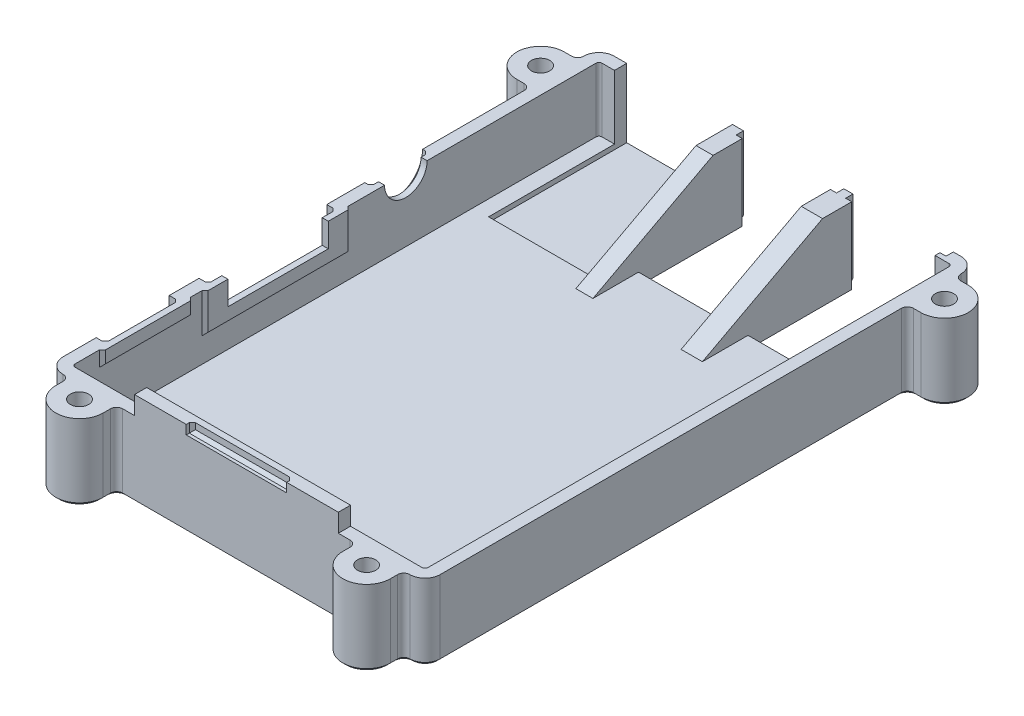
SolidWorks part; units mm, degrees
ref_plane "Front Plane" through (0, 0, 0) normal (0, 0, 1) x (1, 0, 0)
ref_plane "Top Plane" through (0, 0, 0) normal (0, 1, 0) x (1, 0, 0)
ref_plane "Right Plane" through (0, 0, 0) normal (1, 0, 0) x (0, 0, -1)
sketch "Sketch2" plane through (0, 0, 0) normal (0, 1, 0) x (1, 0, 0)
  line L1 (2.5, 0) -> (59.5, 0)
  line L2 (0, 2.5) -> (0, 88.1)
  line L3 (2.5, 90.6) -> (59.5, 90.6)
  line L4 (62, 2.5) -> (62, 88.1)
  arc A0 (0, 2.5) -> (2.5, 0) centre (2.5, 2.5) ccw
  arc A1 (59.5, 0) -> (62, 2.5) centre (59.5, 2.5) ccw
  arc A2 (62, 88.1) -> (59.5, 90.6) centre (59.5, 88.1) ccw
  arc A3 (2.5, 90.6) -> (0, 88.1) centre (2.5, 88.1) ccw
  point P7 (0, 0)
  point P10 (62, 0)
  point P13 (62, 90.6)
  point P16 (0, 90.6)
  dimension "D3" = 2.5
  dimension "D1" = 62
  dimension "D2" = 90.6
extrude "Base" add sketch "Sketch2" along normal blind 12.5
shell "Shell" thickness 2 removed face at (31, 12.5, -45.3)
sketch "Sketch14" plane through (0, 0, 0) normal (0, -1, 0) x (1, 0, 0)
  line L0 (31, 0) -> (31, -90.6) construction
  line L2 (59.5, -90.6) -> (2.5, -90.6) construction
  line L3 (-2.2, -79.3) -> (0, -79.3)
  line L4 (0, -88.1) -> (0, -2.5) construction
  line L5 (0, -79.3) -> (0, -87.1)
  line L6 (0, -87.1) -> (-2.2, -87.1)
  line L7 (3.5, 2.2) -> (3.5, 0)
  line L8 (2.5, 0) -> (59.5, 0) construction
  line L9 (3.5, 0) -> (11.3, 0)
  line L10 (11.3, 0) -> (11.3, 2.2)
  line L11 (64.2, -79.3) -> (62, -79.3)
  line L12 (62, -87.1) -> (64.2, -87.1)
  line L13 (62, -79.3) -> (62, -87.1)
  line L14 (50.7, 0) -> (50.7, 2.2)
  line L15 (58.5, 0) -> (50.7, 0)
  line L16 (58.5, 2.2) -> (58.5, 0)
  line L17 (2.5, 0) -> (59.5, 0) construction
  arc A0 (-2.2, -79.3) -> (-2.2, -87.1) centre (-2.2, -83.2) ccw
  arc A1 (3.5, 2.2) -> (11.3, 2.2) centre (7.4, 2.2) cw
  arc A2 (64.2, -79.3) -> (64.2, -87.1) centre (64.2, -83.2) cw
  arc A3 (58.5, 2.2) -> (50.7, 2.2) centre (54.6, 2.2) ccw
  dimension "D1" = 2.2
  dimension "D2" = 7.8
  dimension "D3" = 3.5
  dimension "D4" = 3.5
extrude "Clamps" add sketch "Sketch14" against normal up to surface (12.5 mm away) up to face at (31, 12.5, -45.3)
fillet "Clamp Fillets" radius 1 8 edges at (50.7, 6.25, 0) (58.5, 6.25, 0) (11.3, 6.25, 0) (3.5, 6.25, 0) (0, 6.25, -87.1) (0, 6.25, -79.3) (62, 6.25, -79.3) (62, 6.25, -87.1)
sketch "Sketch20" plane through (0, 0, 0) normal (0, -1, 0) x (1, 0, 0)
  circle A0 centre (7.4, 2.2) radius 1.5
  circle A1 centre (54.6, 2.2) radius 1.5
  circle A2 centre (64.2, -83.2) radius 1.5
  circle A3 centre (-2.2, -83.2) radius 1.5
  arc A4 (11.3, 2.2) -> (3.5, 2.2) centre (7.4, 2.2) ccw construction
  arc A5 (58.5, 2.2) -> (50.7, 2.2) centre (54.6, 2.2) ccw construction
  arc A6 (-2.2, -79.3) -> (-2.2, -87.1) centre (-2.2, -83.2) ccw construction
  arc A7 (64.2, -87.1) -> (64.2, -79.3) centre (64.2, -83.2) ccw construction
  dimension "D1" = 3
extrude "Clamp Holes" cut sketch "Sketch20" against normal through all
sketch "Sketch21" plane through (0, 0, 0) normal (0, -1, 0) x (1, 0, 0)
  circle A0 centre (7.4, 2.2) radius 2.5
  circle A1 centre (54.6, 2.2) radius 2.5
  circle A2 centre (64.2, -83.2) radius 2.5
  circle A3 centre (-2.2, -83.2) radius 2.5
  circle A4 centre (-2.2, -83.2) radius 1.5 construction
  circle A5 centre (7.4, 2.2) radius 1.5 construction
  circle A6 centre (54.6, 2.2) radius 1.5 construction
  circle A7 centre (64.2, -83.2) radius 1.5 construction
  dimension "D1" = 5
extrude "Clamp Countersinks" cut sketch "Sketch21" against normal blind 3
chamfer "Clamp Countersink Chamfers" distance 0.3 angle 45 4 edges at (-2.2, 0, -85.7) (64.2, 0, -85.7) (54.6, 0, -0.3) (7.4, 0, -0.3)
sketch "Sketch22" plane through (0, 12.5, 0) normal (0, 1, 0) x (1, 0, 0)
  line L0 (31, 2) -> (31, 0) construction
  line L1 (2.5, 2) -> (59.5, 2) construction
  line L2 (12.3, 0) -> (49.7, 0) construction
  line L4 (14.25, 2) -> (47.75, 2)
  line L5 (14.25, 2) -> (14.25, 0)
  line L6 (14.25, 0) -> (47.75, 0)
  line L7 (47.75, 2) -> (47.75, 0)
  dimension "D1" = 16.75
  dimension "D2" = 33.5
extrude "SD Fill" add sketch "Sketch22" along normal blind 3
sketch "Sketch23" plane through (0, 0, 0) normal (0, 0, 1) x (1, 0, 0)
  line L0 (31, 15.5) -> (31, 0) construction
  line L1 (14.25, 15.5) -> (47.75, 15.5) construction
  line L2 (12.3, 0) -> (49.7, 0) construction
  line L4 (22.75, 15.5) -> (39.25, 15.5)
  line L5 (22.75, 15.5) -> (22.75, 14)
  line L6 (22.75, 14) -> (39.25, 14)
  line L7 (39.25, 15.5) -> (39.25, 14)
  dimension "D1" = 8.25
  dimension "D2" = 16.5
  dimension "D3" = 1.5
extrude "SD Approach" cut sketch "Sketch23" against normal blind 1
chamfer "SD Approach Chamfer" distance 0.5 angle 45 3 edges at (39.25, 14.75, -1) (31, 14, -1) (22.75, 14.75, -1)
sketch "Sketch24" plane through (0, 0, -90.6) normal (0, 0, -1) x (-1, 0, 0)
  line L0 (-59.5, 12.5) -> (-2.5, 12.5) construction
  line L1 (-57.25, 12.5) -> (-42.75, 12.5)
  line L2 (-57.25, 12.5) -> (-57.25, 0)
  line L3 (-57.25, 0) -> (-42.75, 0)
  line L4 (-42.75, 12.5) -> (-42.75, 0)
  line L5 (-59.5, 0) -> (-2.5, 0) construction
  line L6 (0, 12.5) -> (0, 0) construction
  line L7 (-39.25, 12.5) -> (-24.75, 12.5)
  line L8 (-39.25, 12.5) -> (-39.25, 0)
  line L9 (-39.25, 0) -> (-24.75, 0)
  line L10 (-24.75, 12.5) -> (-24.75, 0)
  dimension "D1" = 14.5
  dimension "D2" = 24.75
  dimension "D3" = 42.75
extrude "USB Cutout" cut sketch "Sketch24" against normal blind 18.25
sketch "Sketch25" plane through (0, 0, -90.6) normal (0, 0, -1) x (-1, 0, 0)
  line L0 (-42.75, 12.5) -> (-39.25, 12.5) construction
  line L1 (-41.75, 12.5) -> (-58.25, 12.5)
  line L2 (-41.75, 12.5) -> (-41.75, 0)
  line L3 (-41.75, 0) -> (-58.25, 0)
  line L4 (-58.25, 12.5) -> (-58.25, 0)
  line L5 (-59.5, 0) -> (-57.25, 0) construction
  line L6 (-24.75, 12.5) -> (-2.5, 12.5) construction
  line L7 (-23.75, 12.5) -> (-40.25, 12.5)
  line L8 (-23.75, 12.5) -> (-23.75, 0)
  line L9 (-23.75, 0) -> (-40.25, 0)
  line L10 (-40.25, 12.5) -> (-40.25, 0)
  line L11 (-42.75, 0) -> (-39.25, 0) construction
  line L12 (-57.25, 12.5) -> (-57.25, 0) construction
  line L13 (-42.75, 0) -> (-42.75, 12.5) construction
  line L14 (-39.25, 12.5) -> (-39.25, 0) construction
  line L15 (-24.75, 0) -> (-24.75, 12.5) construction
  point P18 (-57.25, 6.25)
  dimension "D1" = 1
  dimension "D2" = 1
  dimension "D3" = 1
  dimension "D4" = 1
extrude "USB Approach" cut sketch "Sketch25" against normal blind 1.2
sketch "Sketch26" plane through (42.75, 0, 0) normal (1, 0, 0) x (0, 0, -1)
  line L0 (88.6, 2) -> (88.6, 12.5)
  line L1 (88.6, 12.5) -> (84.6, 12.5)
  line L2 (88.6, 2) -> (64.8524, 2)
  line L3 (64.8524, 2) -> (84.6, 12.5)
  line L4 (90.6, 0) -> (90.6, 12.5) construction
  dimension "D1" = 6
  dimension "D2" = 28
extrude "USB Inner Support" add sketch "Sketch26" against normal up to surface (3.5 mm away) up to face at (39.25, 4.8333, -83.45)
sketch "Sketch27" plane through (24.75, 0, 0) normal (1, 0, 0) x (0, 0, -1)
  line L0 (88.6, 2) -> (88.6, 12.5)
  line L1 (88.6, 12.5) -> (84.6, 12.5)
  line L2 (88.6, 2) -> (64.8524, 2)
  line L3 (64.8524, 2) -> (84.6, 12.5)
  line L4 (90.6, 0) -> (90.6, 12.5) construction
  dimension "D1" = 6
  dimension "D2" = 28
extrude "USB Outer Support" add sketch "Sketch27" against normal blind 2.8
sketch "Sketch28" plane through (0, 0, -90.6) normal (0, 0, -1) x (-1, 0, 0)
  line L0 (-23.75, 12.5) -> (-2.5, 12.5) construction
  line L1 (-21.95, 12.5) -> (-4.55, 12.5)
  line L2 (-21.95, 12.5) -> (-21.95, 1.2)
  line L3 (-21.95, 1.2) -> (-4.55, 1.2)
  line L4 (-4.55, 12.5) -> (-4.55, 1.2)
  line L5 (0, 12.5) -> (0, 0) construction
  dimension "D1" = 17.4
  dimension "D2" = 4.55
  dimension "D3" = 11.3
extrude "RJ45 Cutout" cut sketch "Sketch28" against normal blind 22.7
sketch "Sketch29" plane through (2, 0, 0) normal (1, 0, 0) x (0, 0, -1)
  line L0 (88.1, 12.5) -> (2.5, 12.5) construction
  line L1 (6.45, 12.5) -> (21.45, 12.5)
  line L2 (6.45, 12.5) -> (6.45, 10)
  line L3 (6.45, 10) -> (21.45, 10)
  line L4 (21.45, 12.5) -> (21.45, 10)
  line L5 (0, 12.5) -> (0, 0) construction
  line L6 (23.35, 12.5) -> (47.35, 12.5)
  line L7 (23.35, 12.5) -> (23.35, 6.07)
  line L8 (23.35, 6.07) -> (47.35, 6.07)
  line L9 (47.35, 12.5) -> (47.35, 6.07)
  dimension "D1" = 24
  dimension "D2" = 15
  dimension "D3" = 6.45
  dimension "D4" = 23.35
  dimension "D5" = 2.5
  dimension "D6" = 6.43
extrude "HDMI Support" add sketch "Sketch29" along normal blind 0.5
chamfer "HDMI Support Chamfer" distance 0.5 angle 45 6 edges at (2.5, 9.285, -47.35) (2.5, 6.07, -35.35) (2.5, 9.285, -23.35) (2.5, 11.25, -21.45) (2.5, 10, -13.95) (2.5, 11.25, -6.45)
sketch "Sketch30" plane through (0, 0, 0) normal (-1, 0, 0) x (0, 0, 1)
  line L0 (-78.3, 12.5) -> (-2.5, 12.5) construction
  line L1 (-24.85, 12.5) -> (-45.85, 12.5)
  line L2 (-24.85, 12.5) -> (-24.85, 6.57)
  line L3 (-24.85, 6.57) -> (-45.85, 6.57)
  line L4 (-45.85, 12.5) -> (-45.85, 6.57)
  line L5 (0, 12.5) -> (0, 0) construction
  line L6 (-19.95, 12.5) -> (-7.95, 12.5)
  line L7 (-19.95, 12.5) -> (-19.95, 10.5)
  line L8 (-19.95, 10.5) -> (-7.95, 10.5)
  line L9 (-7.95, 12.5) -> (-7.95, 10.5)
  dimension "D1" = 12
  dimension "D2" = 21
  dimension "D3" = 7.95
  dimension "D4" = 24.85
  dimension "D5" = 5.93
  dimension "D6" = 2
extrude "HDMI Approach" cut sketch "Sketch30" against normal blind 1.5
sketch "Sketch31" plane through (1.5, 0, 0) normal (-1, 0, 0) x (0, 0, 1)
  line L0 (-24.85, 12.5) -> (-45.85, 12.5) construction
  line L1 (-43.6, 12.5) -> (-27.1, 12.5)
  line L2 (-43.6, 12.5) -> (-43.6, 8.57)
  line L3 (-43.6, 8.57) -> (-27.1, 8.57)
  line L4 (-27.1, 12.5) -> (-27.1, 8.57)
  line L5 (-45.85, 12.5) -> (-45.85, 6.57) construction
  line L6 (-24.85, 6.57) -> (-24.85, 12.5) construction
  line L7 (-45.85, 6.57) -> (-24.85, 6.57) construction
  dimension "D1" = 2.25
  dimension "D2" = 2.25
  dimension "D3" = 2
extrude "HDMI Cutout" cut sketch "Sketch31" against normal blind 1
chamfer "HDMI Approach Chamfer" distance 0.5 angle 45 6 edges at (1.5, 11.5, -7.95) (1.5, 10.5, -13.95) (1.5, 11.5, -19.95) (1.5, 9.535, -24.85) (1.5, 6.57, -35.35) (1.5, 9.535, -45.85)
sketch "Sketch32" plane through (0, 0, 0) normal (-1, 0, 0) x (0, 0, 1)
  line L0 (-78.3, 12.5) -> (-45.85, 12.5) construction
  line L1 (0, 12.5) -> (0, 0) construction
  circle A0 centre (-56.85, 12.5) radius 3.5
  dimension "D1" = 7
  dimension "D2" = 56.85
extrude "Audio Cutout" cut sketch "Sketch32" against normal blind 2
sketch "Sketch33" plane through (0, 0, 0) normal (-1, 0, 0) x (0, 0, 1)
  circle A0 centre (-56.85, 12.5) radius 4.75
  arc A1 (-60.35, 12.5) -> (-53.35, 12.5) centre (-56.85, 12.5) ccw construction
  dimension "D1" = 9.5
extrude "Audio Approach" cut sketch "Sketch33" against normal blind 1
chamfer "Audio Approach Chamfer" distance 0.5 angle 45 1 edges at (1, 7.75, -56.85)
sketch "Sketch34" plane through (0, 0, 0) normal (0, -1, 0) x (1, 0, 0)
  line L0 (62, -2.5) -> (62, -78.3) construction
  line L1 (52.5, -9.4) -> (58.5, -9.4)
  line L2 (52.5, -9.4) -> (52.5, -62.1)
  line L3 (52.5, -62.1) -> (58.5, -62.1)
  line L4 (58.5, -9.4) -> (58.5, -62.1)
  line L5 (12.3, 0) -> (49.7, 0) construction
  point P6 (55.5, -9.4)
  dimension "D1" = 6
  dimension "D2" = 52.7
  dimension "D3" = 3.5
  dimension "D4" = 9.4
extrude "Header Cutout" cut sketch "Sketch34" against normal blind 2
sketch "Sketch35" plane through (0, 0, 0) normal (0, -1, 0) x (1, 0, 0)
  line L0 (55.5, -9.4) -> (55.5, -62.1) construction
  line L1 (58.5, -9.4) -> (52.5, -9.4) construction
  line L2 (52.5, -62.1) -> (58.5, -62.1) construction
  line L3 (52.5, -35.75) -> (58.5, -35.75) construction
  line L4 (52.5, -9.4) -> (52.5, -62.1) construction
  line L5 (58.5, -62.1) -> (58.5, -9.4) construction
  line L6 (56, -9.4) -> (55, -9.4)
  line L7 (55, -9.4) -> (55, -10.4)
  line L8 (55, -10.4) -> (53.5, -10.4)
  line L9 (53.5, -10.4) -> (53.5, -15.3625)
  line L10 (53.5, -15.3625) -> (52.5, -15.3625)
  line L11 (52.5, -15.3625) -> (52.5, -16.3625)
  line L12 (52.5, -16.3625) -> (53.5, -16.3625)
  line L13 (53.5, -16.3625) -> (53.5, -28.2875)
  line L14 (53.5, -28.2875) -> (52.5, -28.2875)
  line L15 (52.5, -28.2875) -> (52.5, -29.2875)
  line L16 (52.5, -29.2875) -> (53.5, -29.2875)
  line L17 (53.5, -29.2875) -> (53.5, -34.25)
  line L18 (53.5, -34.25) -> (55, -34.25)
  line L19 (55, -34.25) -> (55, -35.25)
  line L20 (55, -35.25) -> (52.5, -35.25)
  line L21 (52.5, -35.25) -> (52.5, -36.25)
  line L22 (56, -62.1) -> (55, -62.1)
  line L23 (55, -36.25) -> (52.5, -36.25)
  line L24 (55, -37.25) -> (55, -36.25)
  line L25 (53.5, -37.25) -> (55, -37.25)
  line L26 (53.5, -42.2125) -> (53.5, -37.25)
  line L27 (52.5, -42.2125) -> (53.5, -42.2125)
  line L28 (52.5, -43.2125) -> (52.5, -42.2125)
  line L29 (53.5, -43.2125) -> (52.5, -43.2125)
  line L30 (53.5, -55.1375) -> (53.5, -43.2125)
  line L31 (52.5, -55.1375) -> (53.5, -55.1375)
  line L32 (52.5, -56.1375) -> (52.5, -55.1375)
  line L33 (53.5, -56.1375) -> (52.5, -56.1375)
  line L34 (53.5, -61.1) -> (53.5, -56.1375)
  line L35 (55, -61.1) -> (53.5, -61.1)
  line L36 (55, -62.1) -> (55, -61.1)
  line L37 (56, -62.1) -> (56, -61.1)
  line L38 (56, -61.1) -> (57.5, -61.1)
  line L39 (57.5, -61.1) -> (57.5, -56.1375)
  line L40 (57.5, -56.1375) -> (58.5, -56.1375)
  line L41 (58.5, -56.1375) -> (58.5, -55.1375)
  line L42 (58.5, -55.1375) -> (57.5, -55.1375)
  line L43 (57.5, -55.1375) -> (57.5, -43.2125)
  line L44 (57.5, -43.2125) -> (58.5, -43.2125)
  line L45 (58.5, -43.2125) -> (58.5, -42.2125)
  line L46 (58.5, -42.2125) -> (57.5, -42.2125)
  line L47 (57.5, -42.2125) -> (57.5, -37.25)
  line L48 (57.5, -37.25) -> (56, -37.25)
  line L49 (56, -37.25) -> (56, -36.25)
  line L50 (56, -36.25) -> (58.5, -36.25)
  line L51 (58.5, -35.25) -> (58.5, -36.25)
  line L52 (56, -35.25) -> (58.5, -35.25)
  line L53 (56, -34.25) -> (56, -35.25)
  line L54 (57.5, -34.25) -> (56, -34.25)
  line L55 (57.5, -29.2875) -> (57.5, -34.25)
  line L56 (58.5, -29.2875) -> (57.5, -29.2875)
  line L57 (58.5, -28.2875) -> (58.5, -29.2875)
  line L58 (57.5, -28.2875) -> (58.5, -28.2875)
  line L59 (57.5, -16.3625) -> (57.5, -28.2875)
  line L60 (58.5, -16.3625) -> (57.5, -16.3625)
  line L61 (58.5, -15.3625) -> (58.5, -16.3625)
  line L62 (57.5, -15.3625) -> (58.5, -15.3625)
  line L63 (57.5, -10.4) -> (57.5, -15.3625)
  line L64 (56, -10.4) -> (57.5, -10.4)
  line L65 (56, -9.4) -> (56, -10.4)
  dimension "D1" = 0.5
  dimension "D2" = 1
  dimension "D3" = 1.5
  dimension "D4" = 11.925
extrude "Header Cover" add sketch "Sketch35" against normal blind 1
chamfer "Shell Chamfer" distance 0.5 angle 45 46 edges at (41, 0, -90.6) (58.875, 0, -90.6) (61.2678, 0, -89.8678) (62.2929, 0, -87.3929) (63.6, 0, -87.1) (68.1, 0, -83.2) (63.6, 0, -79.3) (62.2929, 0, -79.0071) (13.125, 0, -90.6) (0.7322, 0, -89.8678) (-0.2929, 0, -87.3929) (-1.6, 0, -87.1) (-6.1, 0, -83.2) (-1.6, 0, -79.3) (-0.2929, 0, -79.0071) (0, 0, -40.4) (0.7322, 0, -0.7322) (3.2071, 0, 0.2929) (3.5, 0, 1.6) (7.4, 0, 6.1) (11.3, 0, 1.6) (11.5929, 0, 0.2929) (31, 0, 0) (50.4071, 0, 0.2929) (50.7, 0, 1.6) (54.6, 0, 6.1) (58.5, 0, 1.6) (58.7929, 0, 0.2929) (61.2678, 0, -0.7322) (62, 0, -40.4) (52.5, 0, -12.3812) (53.75, 0, -9.4) (57.25, 0, -9.4) (58.5, 0, -12.3812) (52.5, 0, -22.325) (58.5, 0, -22.325) (58.5, 0, -32.2687) (52.5, 0, -32.2687) (52.5, 0, -39.2312) (58.5, 0, -39.2312) (58.5, 0, -49.175) (52.5, 0, -49.175) (58.5, 0, -59.1187) (57.25, 0, -62.1) (52.5, 0, -59.1188) (53.75, 0, -62.1)
